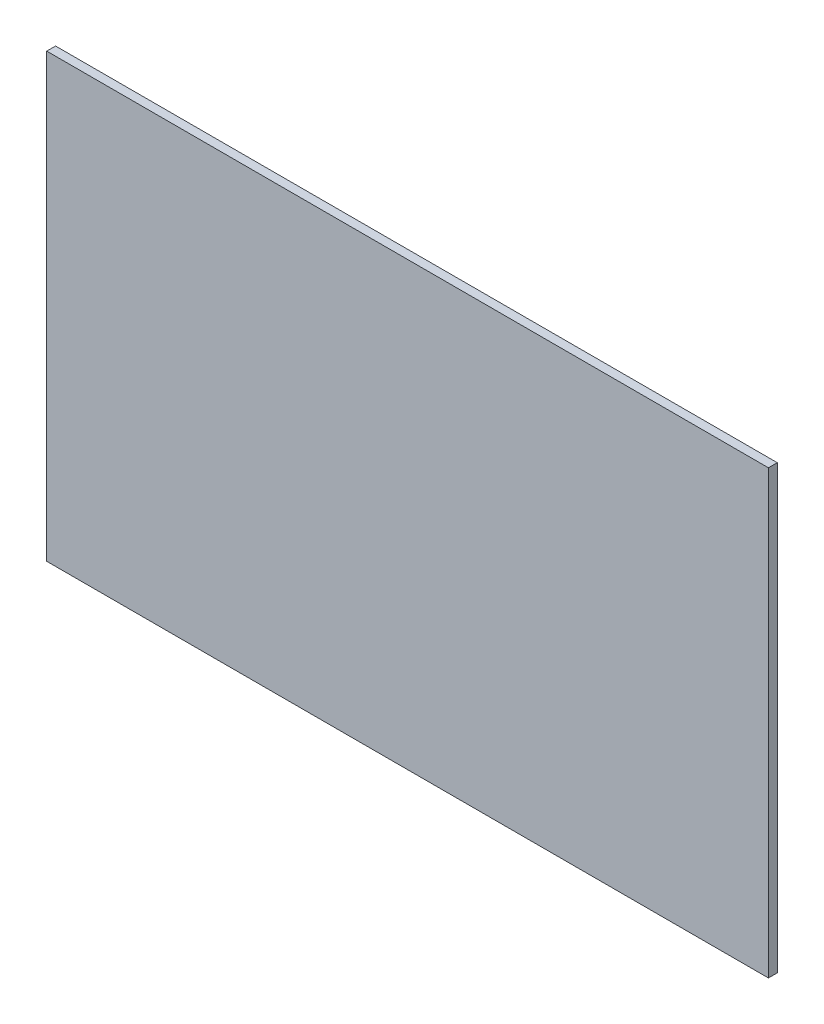
SolidWorks part; units mm, degrees
ref_plane "Front Plane" through (0, 0, 0) normal (0, 0, 1) x (1, 0, 0)
ref_plane "Top Plane" through (0, 0, 0) normal (0, 1, 0) x (1, 0, 0)
ref_plane "Right Plane" through (0, 0, 0) normal (1, 0, 0) x (0, 0, -1)
sketch "Sketch1" plane through (0, 0, 0) normal (0, 0, 1) x (1, 0, 0)
  line L1 (-122.5, 75) -> (122.5, 75)
  line L2 (-122.5, 75) -> (-122.5, -75)
  line L3 (-122.5, -75) -> (122.5, -75)
  line L4 (122.5, 75) -> (122.5, -75)
  line L5 (-122.5, 75) -> (122.5, -75) construction
  line L6 (-122.5, -75) -> (122.5, 75) construction
  point P0 (0, 0)
  dimension "D1" = 150
  dimension "D2" = 245
extrude "Boss-Extrude1" add sketch "Sketch1" along normal blind 3
